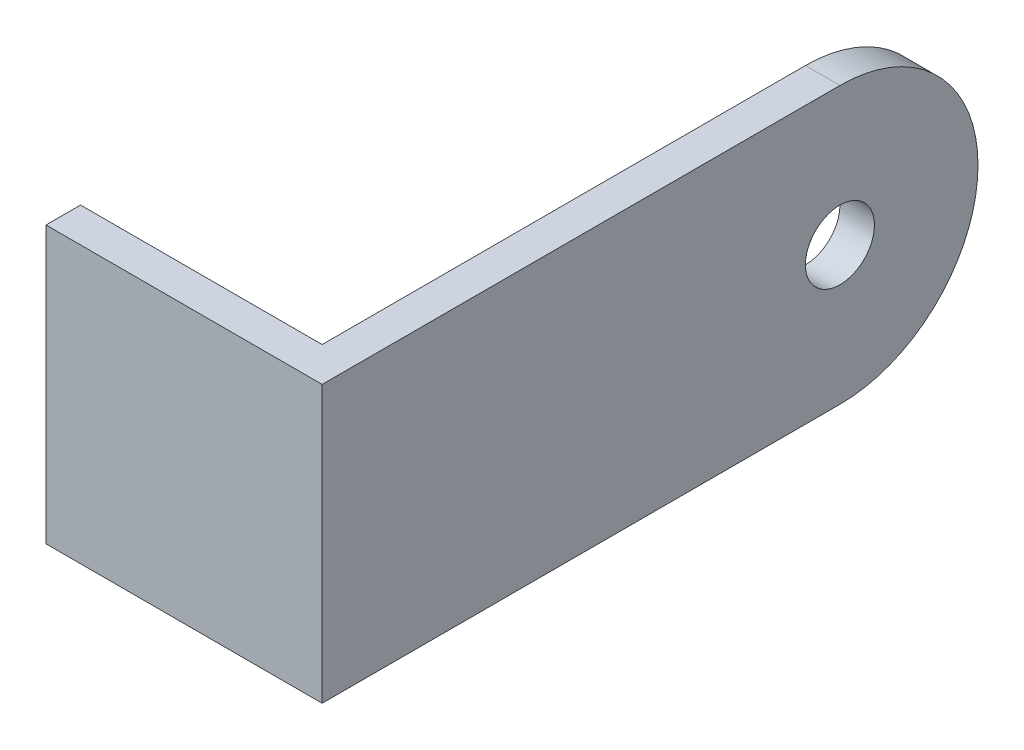
SolidWorks part; units mm, degrees
ref_plane "Front Plane" through (0, 0, 0) normal (0, 0, 1) x (1, 0, 0)
ref_plane "Top Plane" through (0, 0, 0) normal (0, 1, 0) x (1, 0, 0)
ref_plane "Right Plane" through (0, 0, 0) normal (1, 0, 0) x (0, 0, -1)
sketch "Sketch1" plane through (0, 0, 0) normal (0, 1, 0) x (1, 0, 0)
  line L0 (-56.0452, 13.4189) -> (-61.0452, 13.4189)
  line L1 (-61.0452, 13.4189) -> (-61.0452, -76.5811)
  line L2 (-61.0452, -76.5811) -> (-96.0452, -76.5811)
  line L3 (-96.0452, -76.5811) -> (-96.0452, -81.5811)
  line L4 (-96.0452, -81.5811) -> (-56.0452, -81.5811)
  line L5 (-56.0452, -81.5811) -> (-56.0452, 13.4189)
  point P2 (-95.2547, -80.7562)
  point P7 (-96.0452, -76.5811)
  point P8 (0, 0)
extrude "Boss-Extrude1" add sketch "Sketch1" along normal mid plane 40
sketch "Sketch2" plane through (-61.0452, 0, 0) normal (-1, 0, 0) x (0, 0, 1)
  circle A0 centre (6.5811, 0) radius 5
extrude "Cut-Extrude1" cut sketch "Sketch2" against normal blind 40
fillet "Fillet1" radius 20 1 edges at (-58.5452, 20, -13.4189)
fillet "Fillet2" radius 20 1 edges at (-58.5452, -20, -13.4189)
